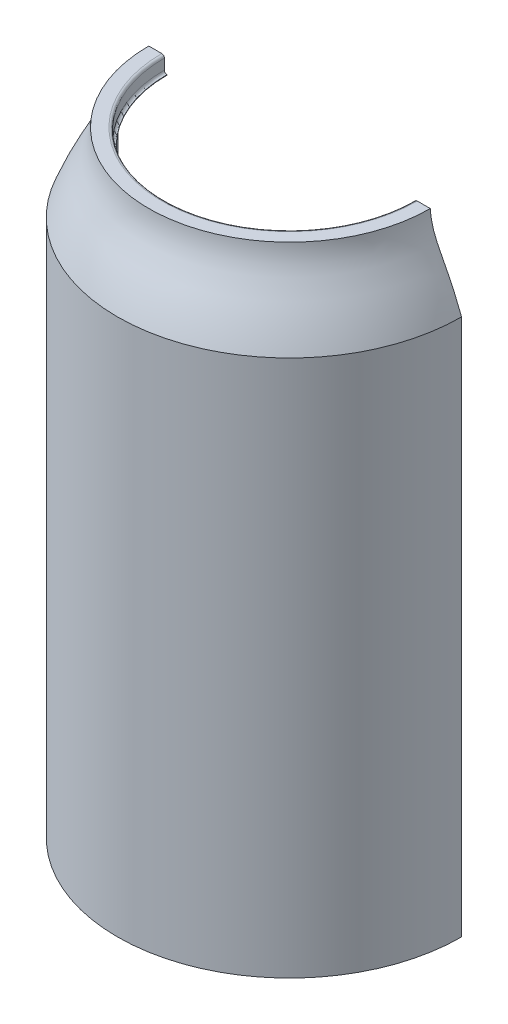
SolidWorks part; units mm, degrees
ref_plane "Alzado" through (0, 0, 0) normal (0, 0, 1) x (1, 0, 0)
ref_plane "Planta" through (0, 0, 0) normal (0, 1, 0) x (1, 0, 0)
ref_plane "Vista lateral" through (0, 0, 0) normal (1, 0, 0) x (0, 0, -1)
sketch "Croquis1" plane through (0, 0, 0) normal (0, 0, 1) x (1, 0, 0)
  line L0 (0, -66.5) -> (0, 66.5) construction
  line L1 (0, 0) -> (33, 0) construction
  line L2 (33, -51.5) -> (33, 51.5)
  line L3 (33, 51.5) -> (33, 66.5) construction
  line L4 (33, -51.5) -> (33, -56.5) construction
  line L5 (27, 66.5) -> (24.5, 66.5)
  line L6 (0, 63.8276) -> (27.4434, 63.8276) construction
  line L7 (25, -56.5) -> (0, -56.5) construction
  line L8 (0, -56.5) -> (0, -46.5) construction
  line L9 (25, -56.5) -> (25.5, -56.5)
  line L10 (0, 66.5) -> (0, -46.5)
  line L11 (0, 63.5) -> (23.5, 63.5)
  line L12 (24, 64) -> (24, 66)
  arc A0 (0, -46.5) -> (25, -56.5) centre (0, -82.75) cw
  arc A1 (24, 64) -> (23.5, 63.5) centre (23.5, 64) cw
  arc A2 (24.5, 66.5) -> (24, 66) centre (24.5, 66) ccw
  spline S0 degree 3 poles (33, 51.5) (29.8693, 59.7715) (27.3334, 61.4597) (27, 66.5) knots 0 0 0 0 0.746651 0.746651 0.746651 0.746651
  spline S1 degree 2 poles (33, -51.5) (27.2132, -53.4506) (25.5, -56.5) knots 0 0 0 0.724921 0.724921 0.724921
  point P4 (0, 0)
  point P10 (33, 0)
  point P25 (24, 63.5)
  dimension "D7" = 10
  dimension "D8" = 0.5
  dimension "D11" = 0.5
  dimension "D1" = 33
  dimension "D2" = 5
  dimension "D3" = 15
  dimension "D4" = 123
  dimension "D5" = 27
  dimension "D6" = 25
  dimension "D9" = 3
  dimension "D10" = 3
revolve "Revolución1" add sketch "Croquis1" angle 360 about L10 region at (16.6287, 6.107, 0)
shell "Vaciado1" thickness 0.1 removed face at (-23.5, 63.5, 0)
sketch "Croquis3" plane through (0, 0, 0) normal (0, 0, 1) x (1, 0, 0)
  line L1 (38.8617, -72.4781) -> (-38.8617, -72.4781)
  line L2 (38.8617, -72.4781) -> (38.8617, 72.4781)
  line L3 (38.8617, 72.4781) -> (-38.8617, 72.4781)
  line L4 (-38.8617, -72.4781) -> (-38.8617, 72.4781)
  line L5 (38.8617, -72.4781) -> (-38.8617, 72.4781) construction
  line L6 (38.8617, 72.4781) -> (-38.8617, -72.4781) construction
  point P0 (0, 0)
extrude "Cortar-Extruir1" cut sketch "Croquis3" against normal blind 40
